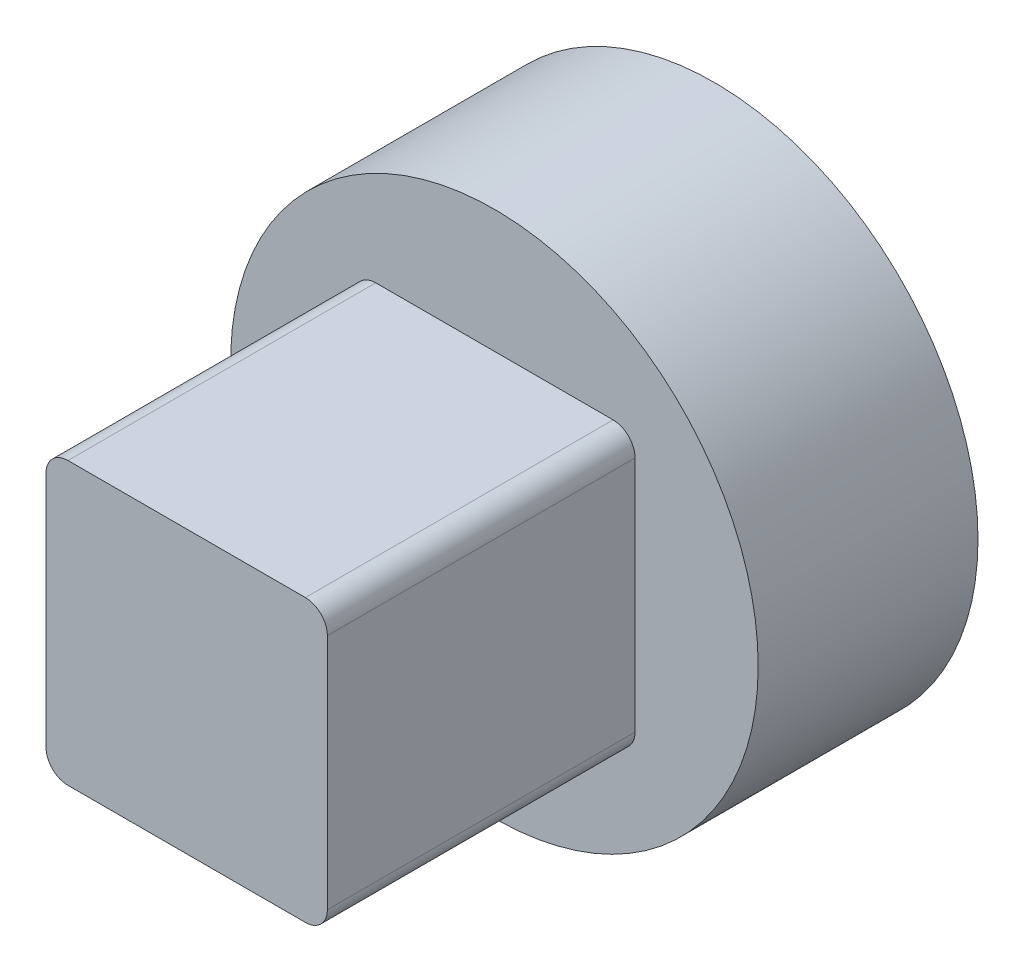
SolidWorks part; units mm, degrees
ref_plane "Front Plane" through (0, 0, 0) normal (0, 0, 1) x (1, 0, 0)
ref_plane "Top Plane" through (0, 0, 0) normal (0, 1, 0) x (1, 0, 0)
ref_plane "Right Plane" through (0, 0, 0) normal (1, 0, 0) x (0, 0, -1)
sketch "Sketch1" plane through (0, 0, -23.4655) normal (0, 0, 1) x (1, 0, 0)
  circle A0 centre (3.7405, -31.8284) radius 2.5
  circle A1 centre (3.7405, -31.8284) radius 6
extrude "Boss-Extrude1" add sketch "Sketch1" along normal blind 5
sketch "Sketch2" plane through (0, 0, -18.4655) normal (0, 0, 1) x (1, 0, 0)
  line L4 (3.7405, -31.8284) -> (6.9405, -31.8284) construction
  line L5 (6.9405, -31.8284) -> (6.9405, -28.6284) construction
  line L7 (6.4405, -28.6284) -> (1.0405, -28.6284)
  line L8 (6.9405, -29.1284) -> (6.9405, -34.5284)
  line L9 (6.4405, -35.0284) -> (1.0405, -35.0284)
  line L10 (0.5405, -29.1284) -> (0.5405, -34.5284)
  arc A1 (0.5405, -29.1284) -> (1.0405, -28.6284) centre (1.0405, -29.1284) cw
  arc A2 (1.0405, -35.0284) -> (0.5405, -34.5284) centre (1.0405, -34.5284) cw
  arc A3 (6.4405, -35.0284) -> (6.9405, -34.5284) centre (6.4405, -34.5284) ccw
  arc A4 (6.4405, -28.6284) -> (6.9405, -29.1284) centre (6.4405, -29.1284) cw
  point P6 (0.5405, -28.6284)
  point P12 (0.5405, -35.0284)
  point P15 (6.9405, -35.0284)
  dimension "D5" = 0.5
  dimension "D6" = 0.5
  dimension "D1" = 3.2
  dimension "D2" = 3.2
  dimension "D3" = 6.4
  dimension "D4" = 6.4
extrude "Boss-Extrude2" add sketch "Sketch2" along normal blind 7
